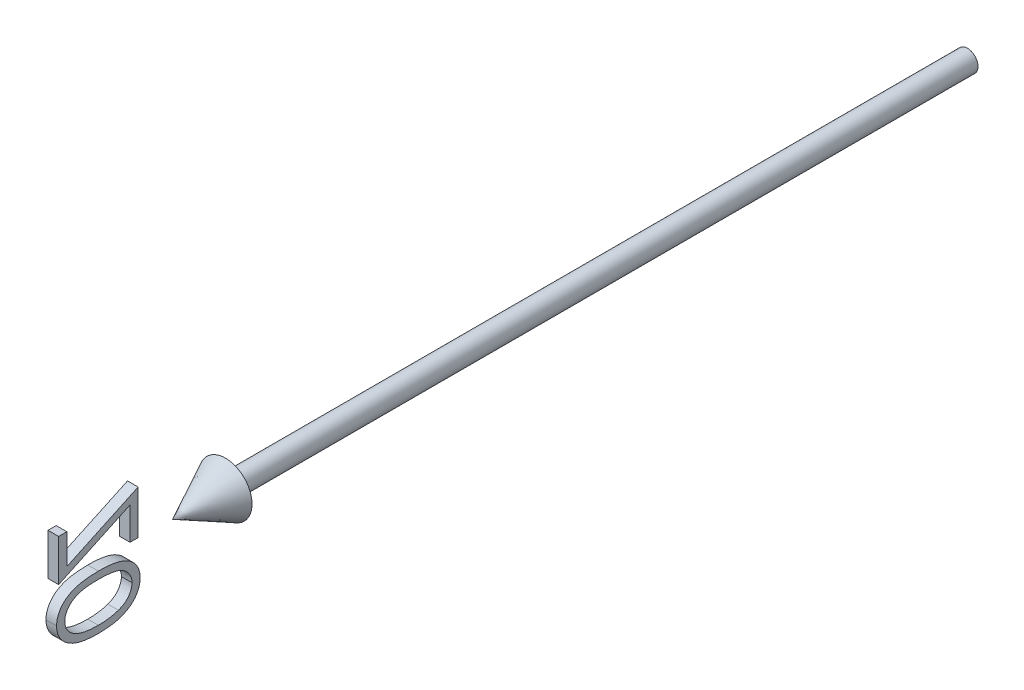
SolidWorks part; units mm, degrees
ref_plane "Front Plane" through (0, 0, 0) normal (0, 0, 1) x (1, 0, 0)
ref_plane "Top Plane" through (0, 0, 0) normal (0, 1, 0) x (1, 0, 0)
ref_plane "Right Plane" through (0, 0, 0) normal (1, 0, 0) x (0, 0, -1)
sketch "Sketch2" plane through (0, 0, 0) normal (0, 1, 0) x (1, 0, 0)
  line L0 (0, 41.95) -> (0, -114.4521) construction
  line L1 (-36.8894, 0) -> (41.4965, 0) construction
  line L2 (0, -150) -> (5, -140)
  line L3 (5, -140) -> (2, -140)
  line L4 (2, -140) -> (2, 0)
  line L5 (2, 0) -> (0, 0)
  line L6 (0, 0) -> (0, -150)
  dimension "D1" = 150
  dimension "D2" = 2
  dimension "D3" = 10
  dimension "D4" = 5
revolve "Revolve1" add sketch "Sketch2" angle 360 about L0
sketch "Sketch3" plane through (0, 0, 0) normal (1, 0, 0) x (0, -1, 0)
  line L0 (0, -101.5706) -> (0, -127.8138) construction
  line L1 (-10.1124, -157.5) -> (14.1256, -157.5) construction
  line L2 (-24.9254, 0) -> (46.7954, 0) construction
  text T0 "Z0" font "Century Gothic" height 15
  dimension "D1" = 157.5
extrude "Boss-Extrude1" add sketch "Sketch3" against normal blind 1 and the other way blind 1 separate body
equation "\"D1@Sketch2\"=\"frame_arrow_length\""
equation "\"D2@Sketch2\"=\"frame_arrow_odA\"/2"
equation "\"D4@Sketch2\"=\"frame_arrow_head_od\""
equation "\"D3@Sketch2\"=\"frame_arrow_head_length\""
equation "\"frame_arrow_length\"=150"
equation "\"frame_arrow_head_length\"=10"
equation "\"frame_arrow_head_od\"=5"
equation "\"frame_arrow_odA\"=4"
equation "\"D1@Sketch3\"=\"frame_arrow_length\"*1.05"
